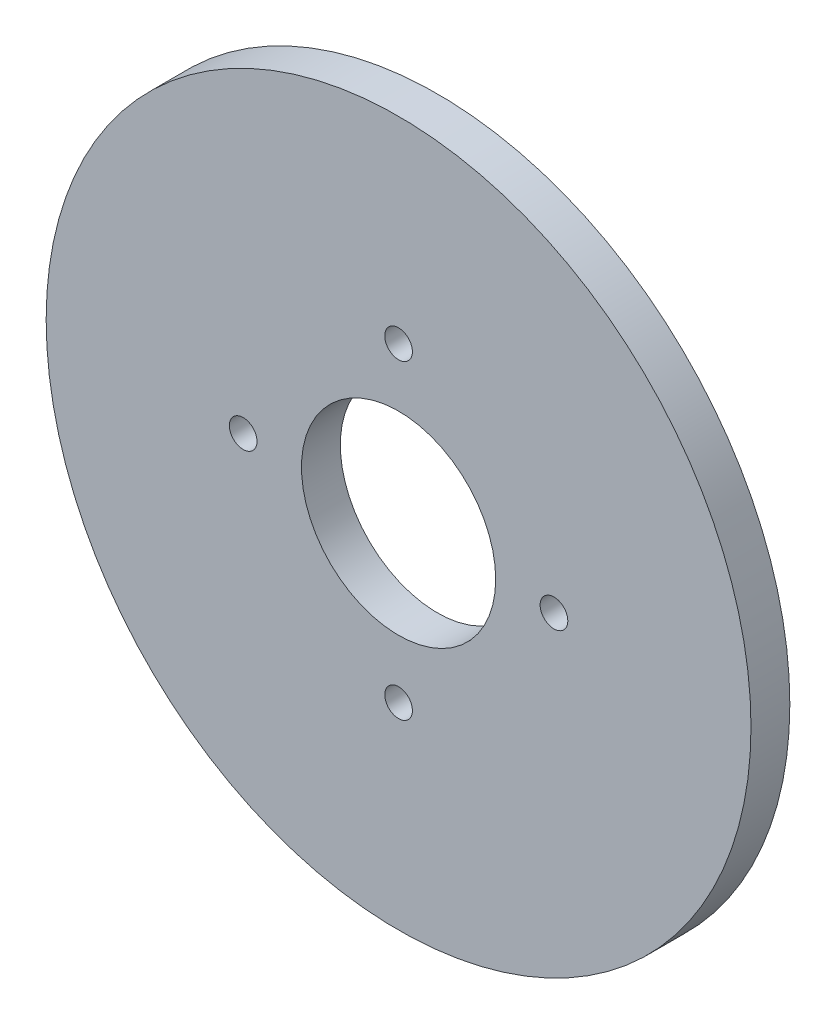
SolidWorks part; units mm, degrees
material "6061 Alloy"
ref_plane "Front Plane" through (0, 0, 0) normal (0, 0, 1) x (1, 0, 0)
ref_plane "Top Plane" through (0, 0, 0) normal (0, 1, 0) x (1, 0, 0)
ref_plane "Right Plane" through (0, 0, 0) normal (1, 0, 0) x (0, 0, -1)
sketch "Sketch1" plane through (0, 0, 0) normal (0, 0, 1) x (1, 0, 0)
  circle A0 centre (0, 0) radius 28.8036
  circle A1 centre (0, 0) radius 7.9375
  dimension "D1" = 57.6072
  dimension "D2" = 15.875
extrude "Boss-Extrude1" add sketch "Sketch1" along normal blind 3.175
hole_wizard "Tap Drill for #4-40 Tap1" positions "Sketch2" profile "Sketch3" hole size "#4-40" standard "ANSI Inch"
sketch "Sketch2" plane through (0, 0, 3.175) normal (0, 0, 1) x (1, 0, 0)
  point P0 (0, 12.7)
  point P2 (0, -12.7)
  point P4 (12.7, 0)
  point P6 (-12.7, 0)
  dimension "D1" = 12.7
  dimension "D2" = 12.7
  dimension "D3" = 12.7
  dimension "D4" = 12.7
sketch "Sketch3" plane through (0, 12.7, 3.175) normal (1, 0, 0) x (0, -1, 0)
  line L0 (0, 0) -> (0, 4.6792)
  line L1 (0, 4.6792) -> (1.1303, 4)
  line L2 (1.1303, 4) -> (1.1303, 0)
  line L5 (1.1303, 0) -> (0, 0)
  line L10 (0, 4.6792) -> (-1.1303, 4) construction
  line L11 (0, -6.35) -> (0, 107.95) construction
  dimension "Hole Dia." = 2.2606
  dimension "Hole Depth" = 4
  dimension "Drill Angle" = 118
